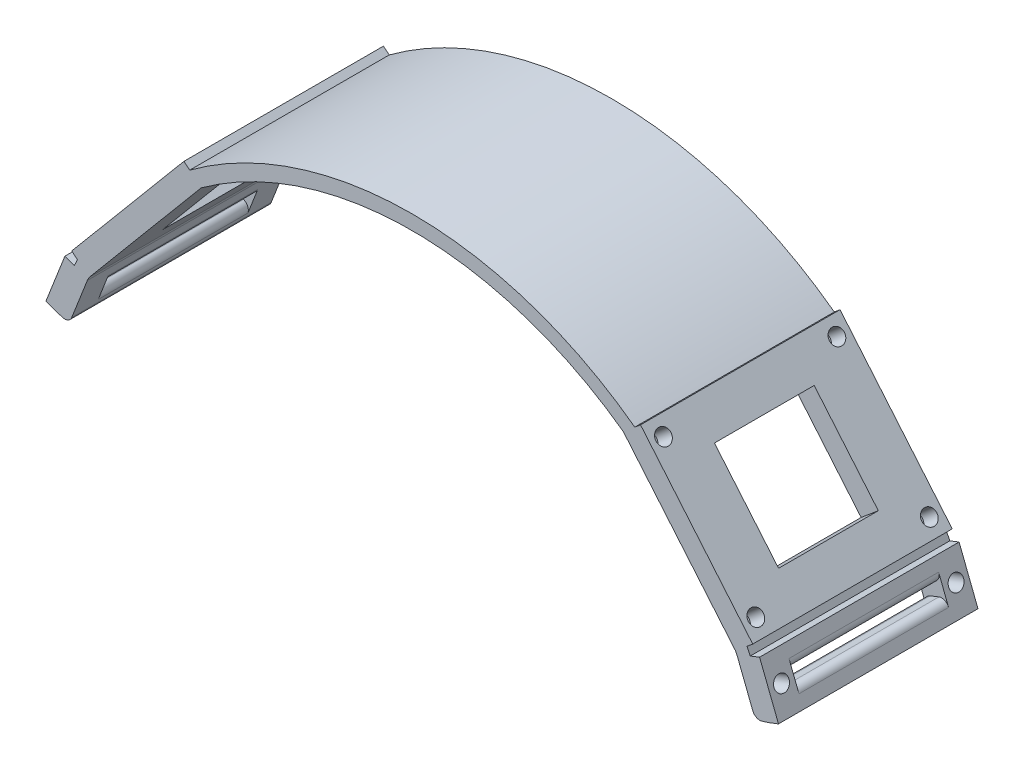
SolidWorks part; units mm, degrees
note: The reader was unsure of these and kept them because the rebuilt part matched: shared geometry of "Sketch15<2>", "Sketch15<3>", "Sketch17<2>", "Sketch17<4>".
material "ABS"
ref_plane "Front Plane" through (0, 0, 0) normal (0, 0, 1) x (1, 0, 0)
ref_plane "Top Plane" through (0, 0, 0) normal (0, 1, 0) x (1, 0, 0)
ref_plane "Right Plane" through (0, 0, 0) normal (1, 0, 0) x (0, 0, -1)
sketch "Sketch2" plane through (0, 0, 0) normal (0, 0, 1) x (1, 0, 0)
  line L0 (-75, 0) -> (75, 0) construction
  line L1 (0, 0) -> (-57.4533, 48.2091) construction
  line L2 (-67.1162, 33.4726) -> (-44.6187, 60.2841)
  line L3 (0, 0) -> (0, 75) construction
  line L4 (-67.1162, 33.4726) -> (-64.8181, 31.5442) construction
  line L5 (-44.6187, 60.2841) -> (-42.3205, 58.3558) construction
  line L6 (-67.7759, 32.1158) -> (-65.1428, 30.8681)
  line L7 (-64.8181, 31.5442) -> (-42.3205, 58.3558)
  line L8 (67.1162, 33.4726) -> (44.6187, 60.2841)
  line L9 (64.8181, 31.5442) -> (42.3205, 58.3558)
  line L10 (67.7759, 32.1158) -> (65.1428, 30.8681)
  line L11 (-65.1428, 30.8681) -> (0, 0) construction
  circle A0 centre (0, 0) radius 75 construction
  circle A1 centre (0, 0) radius 72.0862 construction
  arc A2 (-65.1428, 30.8681) -> (-64.8181, 31.5442) centre (0, 0) cw
  arc A3 (-67.1162, 33.4726) -> (-67.7759, 32.1158) centre (0, 0) ccw
  arc A4 (42.3205, 58.3558) -> (-42.3205, 58.3558) centre (0, 0) ccw
  arc A5 (-44.6187, 60.2841) -> (44.6187, 60.2841) centre (0, 0) cw
  arc A6 (65.1428, 30.8681) -> (64.8181, 31.5442) centre (0, 0) ccw
  arc A7 (67.7759, 32.1158) -> (67.1162, 33.4726) centre (0, 0) ccw
  point P8 (-55.8674, 46.8783)
  dimension "D1" = 150
  dimension "D5" = 0.75
  dimension "D2" = 40
  dimension "D3" = 35
  dimension "D4" = 3
extrude "Boss-Extrude1" add sketch "Sketch2" along normal blind 40
sketch "Sketch8" plane through (-55.8674, 46.8783, 0) normal (-0.766, 0.6428, 0) x (0, 0, 1)
  line L1 (0, 17.5) -> (40, 17.5)
  line L2 (0, 17.5) -> (0, -17.5)
  line L3 (0, -17.5) -> (40, -17.5)
  line L4 (40, 17.5) -> (40, -17.5)
extrude "Boss-Extrude2" add sketch "Sketch8" along normal blind 1.5
sketch "Sketch4" plane through (-53.5693, 44.95, 0) normal (0.766, -0.6428, 0) x (0, 0, -1)
  line L0 (-20, -14.405) -> (-20, -17.5) construction
  line L1 (-2.61, -14.405) -> (-37.39, -14.405) construction
  line L2 (-2.61, -14.405) -> (-2.61, 14.405) construction
  line L3 (-2.61, 14.405) -> (-37.39, 14.405) construction
  line L4 (-37.39, -14.405) -> (-37.39, 14.405) construction
  line L5 (-30, 0) -> (-37.39, 0) construction
  line L6 (-37.39, 0) -> (-40, 0) construction
  line L7 (-40, -17.5) -> (-40, 17.5) construction
  line L8 (-40, -17.5) -> (0, -17.5) construction
  line L9 (-20, 10) -> (-20, 14.405) construction
  line L10 (-2.61, 0) -> (0, 0) construction
  line L11 (0, -17.5) -> (0, 17.5) construction
  line L12 (-20, 14.405) -> (-20, 17.5) construction
  line L13 (-40, 17.5) -> (0, 17.5) construction
  line L14 (-30, -10) -> (-10, -10)
  line L15 (-30, -10) -> (-30, 10)
  line L16 (-30, 10) -> (-10, 10)
  line L17 (-10, -10) -> (-10, 10)
  line L18 (-10, 0) -> (-2.61, 0) construction
  line L19 (-20, -10) -> (-20, -14.405) construction
  circle A0 centre (-37.39, -14.405) radius 1.5
  circle A1 centre (-37.39, 14.405) radius 1.5
  circle A2 centre (-2.61, -14.405) radius 1.5
  circle A3 centre (-2.61, 14.405) radius 1.5
  circle A4 centre (-37.39, -14.405) radius 3
  circle A5 centre (-2.61, -14.405) radius 3
  circle A6 centre (-2.61, 14.405) radius 3
  circle A7 centre (-37.39, 14.405) radius 3
  dimension "D3" = 3
  dimension "D4" = 6
  dimension "D1" = 28.81
  dimension "D2" = 34.78
  dimension "D5" = 20
  dimension "D6" = 20
sketch "Sketch7" plane through (53.5693, 44.95, -58.9576) normal (-0.766, -0.6428, 0) x (0.4132, -0.4924, 0.766)
  line L0 (64.5571, 77.0145) -> (33.9154, 51.303) construction
  line L1 (83.0659, 50.8962) -> (56.4229, 28.54) construction
  line L2 (83.0659, 50.8962) -> (64.5472, 72.9659) construction
  line L3 (64.5472, 72.9659) -> (37.9042, 50.6098) construction
  line L4 (56.4229, 28.54) -> (37.9042, 50.6098) construction
  line L5 (64.5571, 77.0145) -> (87.0547, 50.2029) construction
  line L6 (73.8066, 61.9311) -> (75.8059, 63.6087) construction
  line L7 (47.1635, 39.5749) -> (45.1642, 37.8972) construction
  line L8 (33.9154, 51.303) -> (56.4129, 24.4914) construction
  line L9 (51.2257, 61.7878) -> (49.2363, 64.1588) construction
  line L10 (69.7444, 39.7181) -> (71.7338, 37.3472) construction
  line L11 (87.0547, 50.2029) -> (56.4129, 24.4914) construction
  line L12 (61.7176, 64.8413) -> (46.3967, 51.9855)
  line L13 (46.3967, 51.9855) -> (59.2525, 36.6647)
  line L14 (59.2525, 36.6647) -> (74.5734, 49.5204)
  line L15 (74.5734, 49.5204) -> (61.7176, 64.8413)
  line L16 (66.9129, 43.0925) -> (69.7444, 39.7181) construction
  line L17 (51.2257, 61.7878) -> (54.0572, 58.4134) construction
  line L18 (52.8246, 44.3251) -> (47.1635, 39.5749) construction
  line L19 (68.1455, 57.1809) -> (73.8066, 61.9311) construction
  circle A0 centre (56.4229, 28.54) radius 1.5
  circle A1 centre (37.9042, 50.6098) radius 1.5
  circle A2 centre (83.0659, 50.8962) radius 1.5
  circle A3 centre (64.5472, 72.9659) radius 1.5
  circle A4 centre (64.5472, 72.9659) radius 2.5
  circle A5 centre (83.0659, 50.8962) radius 2.5
  circle A6 centre (37.9042, 50.6098) radius 2.5
  circle A7 centre (56.4229, 28.54) radius 2.5
  dimension "D3" = 3
  dimension "D4" = 5
  dimension "D1" = 28.81
  dimension "D2" = 34.78
  dimension "D5" = 20
  dimension "D6" = 20
sketch "Sketch9" plane through (55.8674, 46.8783, 0) normal (0.766, 0.6428, 0) x (0, 0, -1)
  line L1 (-40, -17.5) -> (0, -17.5)
  line L2 (-40, -17.5) -> (-40, 17.5)
  line L3 (-40, 17.5) -> (0, 17.5)
  line L4 (0, -17.5) -> (0, 17.5)
extrude "Boss-Extrude3" add sketch "Sketch9" along normal blind 1.5
sketch "Sketch11" plane through (-57.0165, 47.8425, 0) normal (-0.766, 0.6428, 0) x (0, 0, 1)
  line L0 (37.39, 0) -> (40, 0) construction
  line L1 (37.39, -14.405) -> (2.61, -14.405) construction
  line L2 (37.39, -14.405) -> (37.39, 14.405) construction
  line L3 (37.39, 14.405) -> (2.61, 14.405) construction
  line L4 (2.61, -14.405) -> (2.61, 14.405) construction
  line L5 (10, 0) -> (2.61, 0) construction
  line L6 (40, -17.5) -> (40, 17.5) construction
  line L9 (20, 10) -> (20, 14.405) construction
  line L10 (2.61, 0) -> (0, 0) construction
  line L12 (0, 17.5) -> (0, -17.5) construction
  line L14 (10, -10) -> (30, -10)
  line L15 (10, -10) -> (10, 10)
  line L16 (10, 10) -> (30, 10)
  line L17 (30, -10) -> (30, 10)
  line L18 (30, 0) -> (37.39, 0) construction
  line L19 (20, -10) -> (20, -14.405) construction
  line L20 (20, -14.405) -> (20, -17.5) construction
  line L21 (0, -17.5) -> (40, -17.5) construction
  line L22 (20, 14.405) -> (20, 17.5) construction
  line L23 (40, 17.5) -> (0, 17.5) construction
  circle A0 centre (2.61, -14.405) radius 1.5
  circle A1 centre (2.61, 14.405) radius 1.5
  circle A2 centre (37.39, -14.405) radius 1.5
  circle A3 centre (37.39, 14.405) radius 1.5
  circle A4 centre (2.61, -14.405) radius 3
  circle A5 centre (37.39, -14.405) radius 3
  circle A6 centre (37.39, 14.405) radius 3
  circle A7 centre (2.61, 14.405) radius 3
  dimension "D3" = 3
  dimension "D4" = 6
  dimension "D1" = 28.81
  dimension "D2" = 34.78
  dimension "D5" = 20
  dimension "D6" = 20
sketch "Sketch12" plane through (57.0165, 47.8425, 58.9576) normal (0.766, 0.6428, 0) x (0.4132, -0.4924, -0.766)
  line L1 (52.4241, 25.1847) -> (25.7811, 2.8285) construction
  line L2 (52.4241, 25.1847) -> (33.9054, 47.2544) construction
  line L3 (33.9054, 47.2544) -> (7.2624, 24.8983) construction
  line L4 (25.7811, 2.8285) -> (7.2624, 24.8983) construction
  line L6 (43.1648, 36.2195) -> (45.1642, 37.8972) construction
  line L7 (16.5217, 13.8634) -> (14.5224, 12.1857) construction
  line L9 (39.1026, 14.0066) -> (41.092, 11.6357) construction
  line L10 (25.7712, -1.2201) -> (56.4129, 24.4914) construction
  line L12 (31.0758, 39.1298) -> (15.7549, 26.274)
  line L13 (15.7549, 26.274) -> (28.6107, 10.9531)
  line L14 (28.6107, 10.9531) -> (43.9316, 23.8089)
  line L15 (43.9316, 23.8089) -> (31.0758, 39.1298)
  line L16 (36.2711, 17.381) -> (39.1026, 14.0066) construction
  line L17 (20.5839, 36.0763) -> (23.4154, 32.7019) construction
  line L18 (22.1828, 18.6136) -> (16.5217, 13.8634) construction
  line L19 (37.5037, 31.4693) -> (43.1648, 36.2195) construction
  line L20 (3.2736, 25.5915) -> (25.7712, -1.2201) construction
  line L21 (56.4129, 24.4914) -> (33.9154, 51.303) construction
  line L22 (20.5839, 36.0763) -> (18.5945, 38.4472) construction
  line L23 (33.9154, 51.303) -> (3.2736, 25.5915) construction
  circle A0 centre (25.7811, 2.8285) radius 1.5
  circle A1 centre (7.2624, 24.8983) radius 1.5
  circle A2 centre (52.4241, 25.1847) radius 1.5
  circle A3 centre (33.9054, 47.2544) radius 1.5
  circle A4 centre (33.9054, 47.2544) radius 2.5
  circle A5 centre (52.4241, 25.1847) radius 2.5
  circle A6 centre (7.2624, 24.8983) radius 2.5
  circle A7 centre (25.7811, 2.8285) radius 2.5
  dimension "D3" = 3
  dimension "D4" = 5
  dimension "D1" = 28.81
  dimension "D2" = 34.78
  dimension "D5" = 20
  dimension "D6" = 20
extrude "Cut-Extrude1" cut sketch "Sketch11" against normal blind 3.75 contours A3 | A1 | A0 | A2
extrude "Cut-Extrude2" cut sketch "Sketch12" against normal blind 3.75 contours A0 | A2 | A3 | A1
extrude "Cut-Extrude3" cut sketch "Sketch4" against normal up to surface (4.5 mm away) contours L14 L17 L16 L15 up to face at (-67.24, 35.6586, 37.39)
extrude "Cut-Extrude4" cut sketch "Sketch7" against normal up to surface (4.5 mm away) contours L14 L15 L12 L13 up to face at (46.793, 60.0265, 37.39)
sketch "Sketch14" plane through (0, 0, 0) normal (0, 0, 1) x (1, 0, 0)
  line L0 (-75, 0) -> (75, 0) construction
  line L1 (0, 0) -> (-57.4533, 48.2091) construction
  line L2 (-67.1162, 33.4726) -> (-44.6187, 60.2841)
  line L3 (0, 0) -> (0, 75) construction
  line L4 (-67.1162, 33.4726) -> (-64.8181, 31.5442) construction
  line L5 (-44.6187, 60.2841) -> (-42.3205, 58.3558) construction
  line L6 (-67.7759, 32.1158) -> (-65.1428, 30.8681)
  line L7 (-64.8181, 31.5442) -> (-42.3205, 58.3558)
  line L8 (67.1162, 33.4726) -> (44.6187, 60.2841)
  line L9 (64.8181, 31.5442) -> (42.3205, 58.3558)
  line L10 (67.7759, 32.1158) -> (65.1428, 30.8681)
  line L11 (-65.1428, 30.8681) -> (0, 0) construction
  line L12 (0, 0) -> (-68.7878, 21.5561) construction
  line L13 (-68.7878, 21.5561) -> (-71.5682, 22.4274)
  line L14 (-71.5682, 22.4274) -> (-67.7759, 32.1158)
  line L15 (-68.7878, 21.5561) -> (-65.1428, 30.8681)
  line L16 (71.5682, 22.4274) -> (67.7759, 32.1158)
  line L17 (68.7878, 21.5561) -> (71.5682, 22.4274)
  line L18 (68.7878, 21.5561) -> (65.1428, 30.8681)
  circle A0 centre (0, 0) radius 75 construction
  circle A1 centre (0, 0) radius 72.0862 construction
  arc A2 (-65.1428, 30.8681) -> (-64.8181, 31.5442) centre (0, 0) cw
  arc A3 (-67.1162, 33.4726) -> (-67.7759, 32.1158) centre (0, 0) ccw
  arc A4 (42.3205, 58.3558) -> (-42.3205, 58.3558) centre (0, 0) ccw
  arc A5 (-44.6187, 60.2841) -> (44.6187, 60.2841) centre (0, 0) cw
  arc A6 (65.1428, 30.8681) -> (64.8181, 31.5442) centre (0, 0) ccw
  arc A7 (67.7759, 32.1158) -> (67.1162, 33.4726) centre (0, 0) ccw
  point P8 (-55.8674, 46.8783)
  dimension "D1" = 150
  dimension "D5" = 0.75
  dimension "D2" = 40
  dimension "D3" = 35
  dimension "D4" = 3
  dimension "D6" = 10
extrude "Boss-Extrude5" add sketch "Sketch14" along normal up to surface (40 mm away) contours L13 L15 L6 L14 | L18 L17 L16 L10 up to face at (0, 44.5689, 40)
sketch "Sketch15" plane through (-69.6721, 27.2716, 0) normal (0.9312, -0.3645, 0) x (0, 0, -1)
  line L0 (-20, -1.25) -> (-20, -5) construction
  line L1 (-35, -1.25) -> (-5, -1.25)
  line L2 (-35, -1.25) -> (-35, 1.25)
  line L3 (-35, 1.25) -> (-5, 1.25)
  line L4 (-5, -1.25) -> (-5, 1.25)
  line L5 (-40, -5) -> (0, -5) construction
  line L6 (-20, 1.25) -> (-20, 5) construction
  line L7 (-40, 5) -> (0, 5) construction
  line L8 (-35, 0) -> (-40, 0) construction
  line L9 (-40, -5) -> (-40, 5) construction
  line L10 (-5, 0) -> (0, 0) construction
  line L11 (0, -5) -> (0, 5) construction
  line L13 (0, 5.2021) -> (-40, 5.2021)
  line L14 (0, 5.2021) -> (0, -5.2021)
  line L15 (0, -5.2021) -> (-40, -5.2021)
  line L16 (-40, 5.2021) -> (-40, -5.2021)
  circle A0 centre (-37.5, 0) radius 1.5
  circle A1 centre (-2.5, 0) radius 1.5
  dimension "D2" = 3
  dimension "D1" = 30
  dimension "D3" = 2.5
sketch "Sketch17" plane through (69.6721, 27.2716, 0) normal (-0.9312, -0.3645, 0) x (0, 0, 1)
  line L0 (20, -1.25) -> (20, -5) construction
  line L1 (5, -1.25) -> (35, -1.25)
  line L2 (5, -1.25) -> (5, 1.25)
  line L3 (5, 1.25) -> (35, 1.25)
  line L4 (35, -1.25) -> (35, 1.25)
  line L6 (20, 1.25) -> (20, 5) construction
  line L7 (40, -5.2021) -> (0, -5.2021)
  line L8 (5, 0) -> (0, 0) construction
  line L9 (40, -5.2021) -> (40, 5.2021)
  line L10 (35, 0) -> (40, 0) construction
  line L11 (40, 5.2021) -> (0, 5.2021)
  line L12 (40, -5) -> (40, 5) construction
  line L13 (0, -5) -> (0, 5) construction
  line L14 (40, -5) -> (0, -5) construction
  line L15 (40, 5) -> (0, 5) construction
  line L16 (0, -5.2021) -> (0, 5.2021)
  circle A0 centre (2.5, 0) radius 1.5
  circle A1 centre (37.5, 0) radius 1.5
  dimension "D2" = 3
  dimension "D1" = 30
  dimension "D3" = 2.5
extrude "Boss-Extrude6" add sketch "Sketch15" against normal blind 2
extrude "Cut-Extrude5" cut sketch "Sketch15<2>" along normal up to surface (2.9068 mm away) contours L4 L1 L2 L3 up to face at (-66.9653, 26.2121, 20)
sketch "Sketch15<2>" plane through (-69.6721, 27.2716, 0) normal (0.9312, -0.3645, 0) x (0, 0, -1) same geometry as "Sketch15"
extrude "Cut-Extrude6" cut sketch "Sketch15<3>" along normal offset from surface (2.1568 mm away) 0.75 contours A0 | A1 up to face at (-66.9653, 26.2121, 20)
sketch "Sketch15<3>" plane through (-69.6721, 27.2716, 0) normal (0.9312, -0.3645, 0) x (0, 0, -1) same geometry as "Sketch15"
extrude "Boss-Extrude7" add sketch "Sketch17" against normal blind 2
extrude "Cut-Extrude7" cut sketch "Sketch17<2>" along normal offset from surface (2.1568 mm away) 0.75 contours A1 | A0 up to face at (66.9653, 26.2121, 20)
sketch "Sketch17<2>" plane through (69.6721, 27.2716, 0) normal (-0.9312, -0.3645, 0) x (0, 0, 1) same geometry as "Sketch17"
extrude "Cut-Extrude9" cut sketch "Sketch17<4>" along normal up to surface (2.9068 mm away) contours L4 L1 L2 L3 up to face at (66.9653, 26.2121, 20)
sketch "Sketch17<4>" plane through (69.6721, 27.2716, 0) normal (-0.9312, -0.3645, 0) x (0, 0, 1) same geometry as "Sketch17"
fillet "Fillet1" radius 1.5 10 edges at (-71.0788, 29.1646, 20) (-71.9901, 26.8366, 20) (-67.4209, 25.0481, 20) (-66.5096, 27.3761, 20) (-68.7878, 21.5561, 20) (71.0788, 29.1646, 20) (71.9901, 26.8366, 20) (67.4209, 25.0481, 20) (66.5096, 27.3761, 20) (68.7878, 21.5561, 20)
